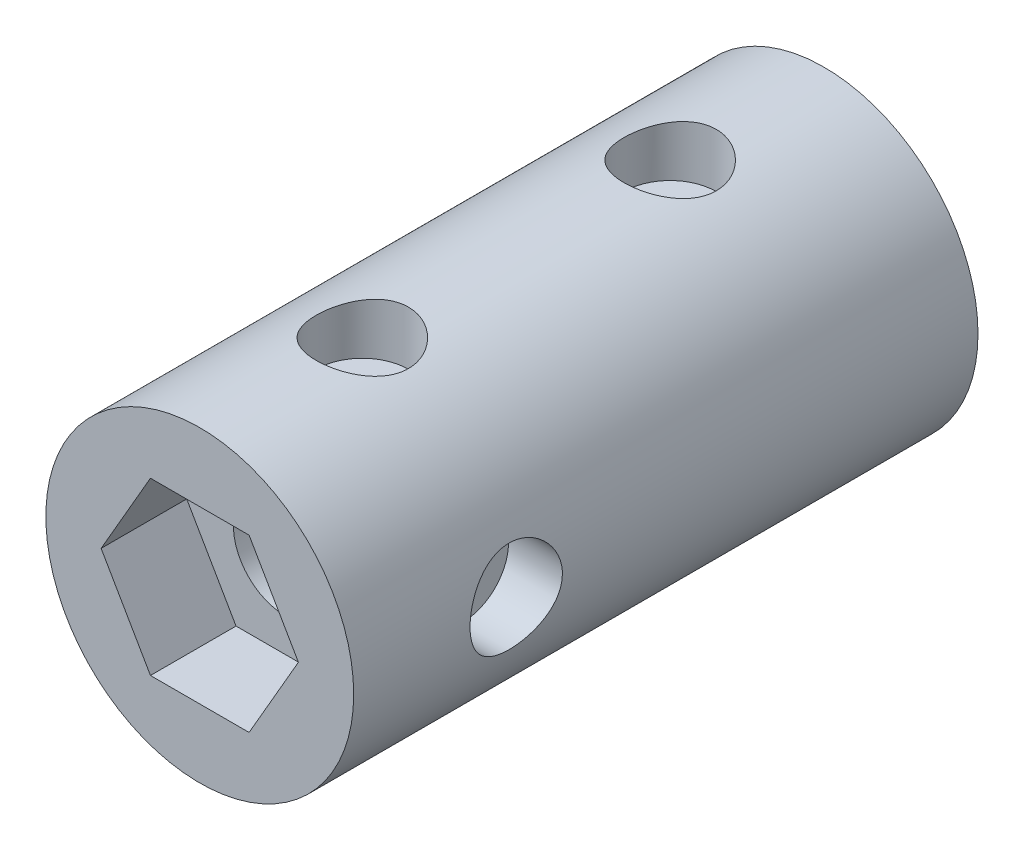
SolidWorks part; units mm, degrees
ref_plane "Front Plane" through (0, 0, 0) normal (0, 0, 1) x (1, 0, 0)
ref_plane "Top Plane" through (0, 0, 0) normal (0, 1, 0) x (1, 0, 0)
ref_plane "Right Plane" through (0, 0, 0) normal (1, 0, 0) x (0, 0, -1)
sketch "Sketch1" plane through (0, 0, 0) normal (0, 0, 1) x (1, 0, 0)
  circle A0 centre (0, 0) radius 2.6
  circle A1 centre (0, 0) radius 10
  dimension "D1" = 5.2
  dimension "D2" = 20
extrude "Boss-Extrude1" add sketch "Sketch1" along normal blind 25
sketch "Sketch2" plane through (0, 0, 25) normal (0, 0, 1) x (1, 0, 0)
  circle A0 centre (0, 0) radius 10
  circle A1 centre (0, 0) radius 10 construction
extrude "Boss-Extrude2" add sketch "Sketch2" against normal blind 5
sketch "Sketch3" plane through (0, 0, 0) normal (0, 1, 0) x (1, 0, 0)
  line L0 (0, 0) -> (0, -10) construction
  line L1 (2.6, 0) -> (-2.6, 0) construction
  circle A0 centre (0, -10) radius 1.35
  dimension "D1" = 2.7
  dimension "D2" = 10
extrude "Cut-Extrude1" cut sketch "Sketch3" against normal through all both and the other way through all
sketch "Sketch6" plane through (0, 0, 25) normal (0, 0, 1) x (1, 0, 0)
  circle A0 centre (0, 0) radius 3.3734
  circle A1 centre (0, 0) radius 10
  circle A2 centre (0, 0) radius 10 construction
  dimension "D1" = 6.7469
extrude "Boss-Extrude4" add sketch "Sketch6" along normal blind 10
sketch "Sketch7" plane through (0, 0, 0) normal (0, 1, 0) x (1, 0, 0)
  line L0 (0, 0) -> (0, -30) construction
  line L1 (-3.3734, -35) -> (3.3734, -35) construction
  circle A0 centre (0, -30) radius 1.35
  dimension "D1" = 2.7
  dimension "D2" = 5
extrude "Cut-Extrude2" cut sketch "Sketch7" against normal through all both and the other way through all
sketch "Sketch8" plane through (0, 0, 0) normal (1, 0, 0) x (0, 0, -1)
  line L0 (0, 0) -> (-30, 0) construction
  line L1 (-35, 10) -> (-35, -10) construction
  circle A0 centre (-30, 0) radius 1.35
  dimension "D1" = 2.7
  dimension "D2" = 5
extrude "Cut-Extrude3" cut sketch "Sketch8" against normal through all both and the other way through all
sketch "Sketch5" plane through (0, 0, 35) normal (0, 0, 1) x (1, 0, 0)
  line L1 (3.2043, -5.55) -> (6.4086, 0)
  line L2 (6.4086, 0) -> (3.2043, 5.55)
  line L3 (3.2043, 5.55) -> (-3.2043, 5.55)
  line L4 (-3.2043, 5.55) -> (-6.4086, 0)
  line L5 (-6.4086, 0) -> (-3.2043, -5.55)
  line L6 (-3.2043, -5.55) -> (3.2043, -5.55)
  circle A0 centre (0, 0) radius 5.55 construction
  circle A1 centre (0, 0) radius 10
  circle A2 centre (0, 0) radius 10 construction
  dimension "D1" = 11.1
extrude "Boss-Extrude3" add sketch "Sketch5" along normal blind 5.56
sketch "Sketch9" plane through (0, 0, 0) normal (0, 1, 0) x (1, 0, 0)
  circle A0 centre (0, -10) radius 3
  circle A1 centre (0, -10) radius 1.35 construction
  dimension "D1" = 6
extrude "Cut-Extrude4" cut sketch "Sketch9" against normal blind 25.4 from offset 6.5 offset against normal yes
mirror "Mirror1" about plane through (0, 0, 0) normal (0, 1, 0) of "Cut-Extrude4"
sketch "Sketch10" plane through (0, 0, 0) normal (0, 1, 0) x (1, 0, 0)
  circle A0 centre (0, -30) radius 3
  circle A1 centre (0, -10) radius 3 construction
extrude "Cut-Extrude5" cut sketch "Sketch10" against normal blind 25.4 from offset 6.5 offset against normal yes
ref_axis "Axis1" through (0, 0, 40.56) along (0, 0, -1)
pattern_circular "CirPattern1" count 4 every 90 about axis through (0, 0, 40.56) along (0, 0, -1) of "Cut-Extrude5"
